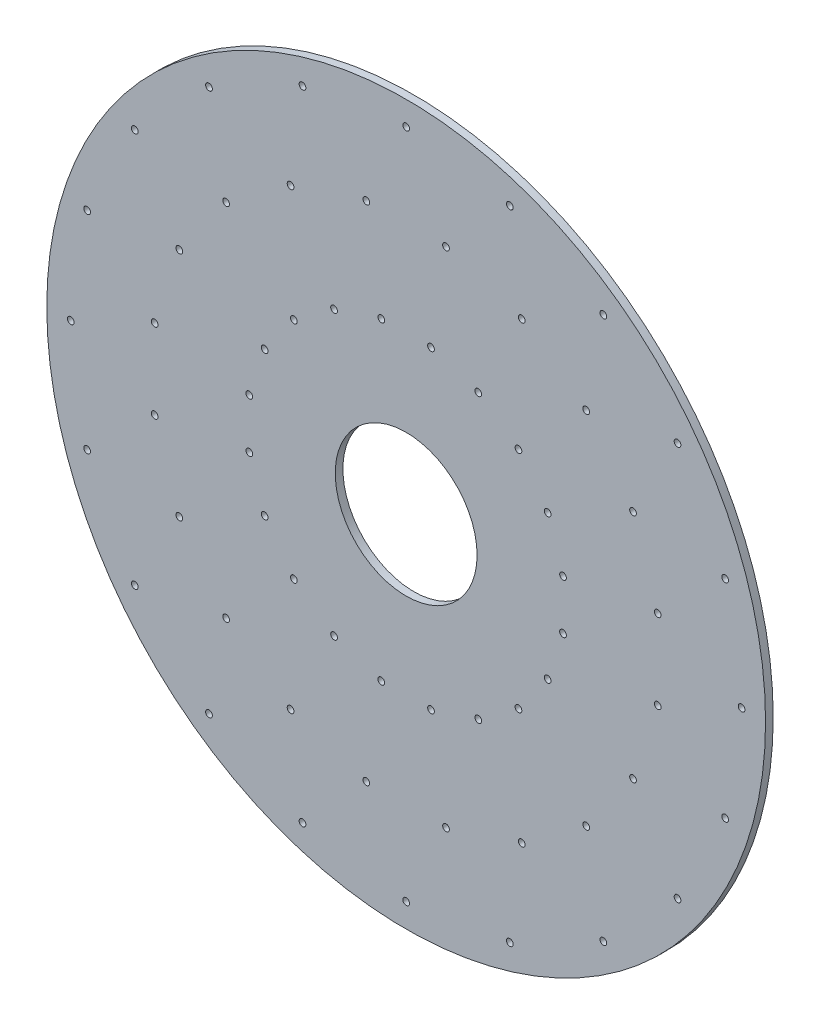
SolidWorks part; units mm, degrees
material "Corrugated Paper"
ref_plane "Front Plane" through (0, 0, 0) normal (0, 0, 1) x (1, 0, 0)
ref_plane "Top Plane" through (0, 0, 0) normal (0, 1, 0) x (1, 0, 0)
ref_plane "Right Plane" through (0, 0, 0) normal (1, 0, 0) x (0, 0, -1)
sketch "Sketch1" plane through (0, 0, 0) normal (0, 0, 1) x (1, 0, 0)
  circle A0 centre (0, 0) radius 187.5
  dimension "D1" = 375
extrude "Boss-Extrude1" add sketch "Sketch1" along normal blind 4
sketch "Sketch2" plane through (0, 0, 4) normal (0, 0, 1) x (1, 0, 0)
  circle A0 centre (0, 0) radius 37
  dimension "D1" = 74
extrude "Cut-Extrude1" cut sketch "Sketch2" against normal through all
sketch "Sketch3" plane through (0, 0, 4) normal (0, 0, 1) x (1, 0, 0)
  line L0 (0, -2.2) -> (0, 2.2) construction
  circle A0 centre (0, 175) radius 1.755
  circle A1 centre (0, 0) radius 187.5 construction
  dimension "D2" = 3.51
  dimension "D1" = 175
extrude "Cut-Extrude2" cut sketch "Sketch3" against normal through all
ref_axis "Axis1" through (0, 0, -0.2) along (0, 0, 1)
pattern_circular "CirPattern1" count 20 over 360 about axis through (0, 0, -0.2) along (0, 0, 1) of "Cut-Extrude2"
sketch "Sketch4" plane through (0, 0, 0) normal (0, 0, -1) x (-1, 0, 0)
  circle A0 centre (-12.9599, -81.8255) radius 1.755 construction
  circle A1 centre (-20.7816, -131.2099) radius 1.755 construction
  circle A2 centre (-12.9599, -81.8255) radius 1.755
  circle A3 centre (-20.7816, -131.2099) radius 1.755
extrude "Cut-Extrude3" cut sketch "Sketch4" against normal through all
pattern_circular "CirPattern2" count 20 over 360 about axis through (0, 0, -0.2) along (0, 0, 1) of "Cut-Extrude3"
